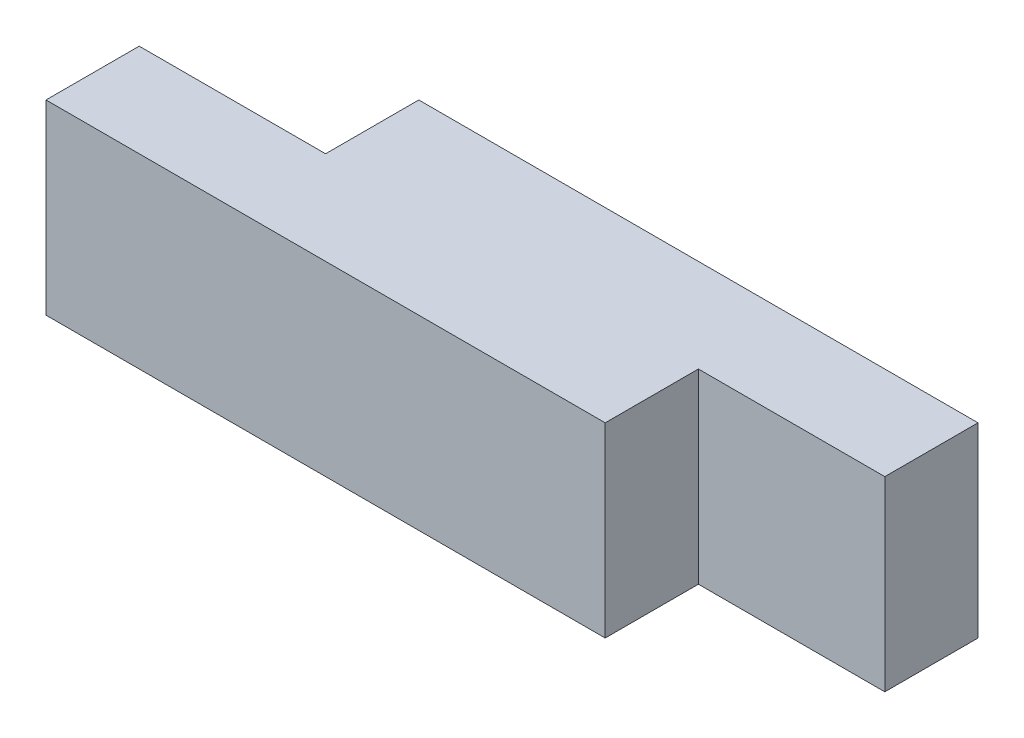
SolidWorks part; units mm, degrees
ref_plane "Alzado" through (0, 0, 0) normal (0, 0, 1) x (1, 0, 0)
ref_plane "Planta" through (0, 0, 0) normal (0, 1, 0) x (1, 0, 0)
ref_plane "Vista lateral" through (0, 0, 0) normal (1, 0, 0) x (0, 0, -1)
sketch "Croquis1" plane through (0, 0, 0) normal (0, 0, 1) x (1, 0, 0)
  line L0 (40, 0) -> (-40, 0) construction
  line L1 (-40, 10) -> (40, 10)
  line L2 (40, 10) -> (40, -10)
  line L3 (40, -10) -> (-40, -10)
  line L4 (-40, -10) -> (-40, 10)
  point P4 (0, 0)
  point P7 (-40, 0)
  dimension "D1" = 80
  dimension "D2" = 20
extrude "Saliente-Extruir1" add sketch "Croquis1" along normal blind 20
sketch "Croquis2" plane through (0, 0, 20) normal (0, 0, 1) x (1, 0, 0)
  line L0 (0, 0) -> (0, 5.7256) construction
  line L7 (20, -10) -> (40, -10)
  line L8 (20, 10) -> (20, -10)
  line L9 (40, 10) -> (20, 10)
  line L10 (40, -10) -> (40, 10)
  dimension "D1" = 20
extrude "Cortar-Extruir1" cut sketch "Croquis2" against normal blind 10
sketch "Croquis3" plane through (0, 0, 0) normal (0, 0, -1) x (-1, 0, 0)
  line L0 (40, 10) -> (20, 10)
  line L1 (-40, 10) -> (40, 10) construction
  line L2 (20, 10) -> (20, -10)
  line L3 (40, -10) -> (-40, -10) construction
  line L4 (20, -10) -> (40, -10)
  line L5 (40, -10) -> (40, 10)
  dimension "D1" = 20
extrude "Cortar-Extruir2" cut sketch "Croquis3" against normal blind 10
